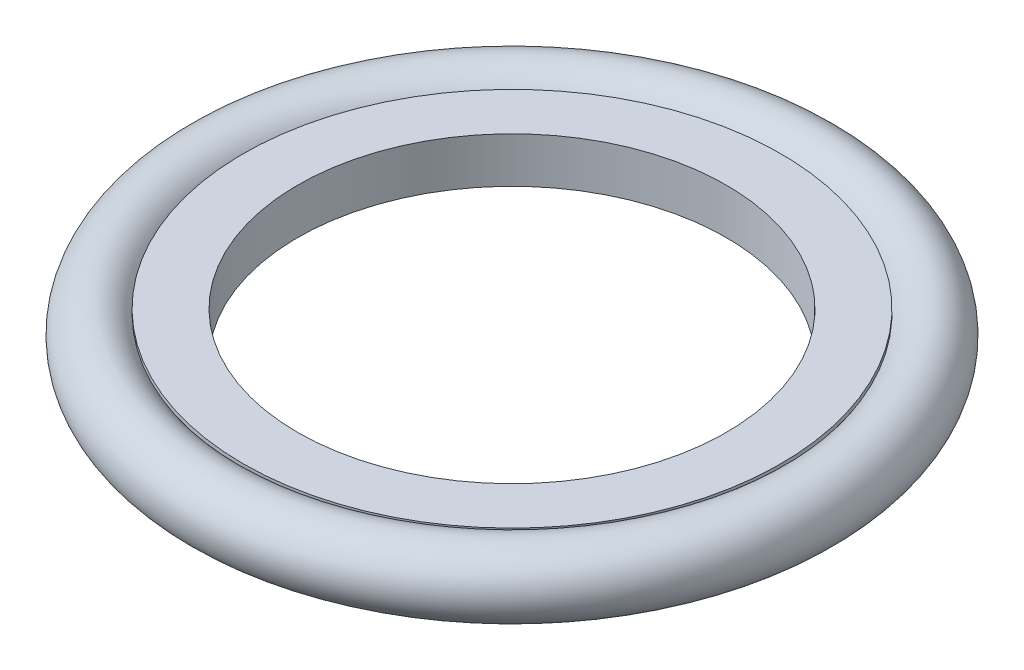
SolidWorks part; units mm, degrees
ref_plane "Front Plane" through (0, 0, 0) normal (0, 0, 1) x (1, 0, 0)
ref_plane "Top Plane" through (0, 0, 0) normal (0, 1, 0) x (1, 0, 0)
ref_plane "Right Plane" through (0, 0, 0) normal (1, 0, 0) x (0, 0, -1)
sketch "Sketch2" plane through (0, 0, 0) normal (1, 0, 0) x (0, 0, -1)
  line L0 (0, 0) -> (209.55, 0) construction
  line L1 (139.7, 0) -> (-139.7, 0) construction
  line L2 (209.55, 0) -> (254, 0) construction
  line L3 (209.55, 17.4625) -> (209.55, -17.4625) construction
  line L4 (0, 0) -> (0, -50000) construction
  circle A0 centre (228.3449, 0) radius 25.6551
  point P8 (209.55, 0)
  dimension "D4" = 51.3103
  dimension "D1" = 209.55
  dimension "D2" = 254
  dimension "D3" = 34.925
revolve "Revolve2" add sketch "Sketch2" angle 360 about L4
sketch "Sketch3" plane through (0, 0, 0) normal (1, 0, 0) x (0, 0, -1)
  line L0 (228.3449, 0) -> (50228.3449, 0) construction
  line L9 (209.6092, 17.526) -> (209.6092, -17.526) construction
  line L10 (207.0791, 17.526) -> (207.0791, 14.351)
  line L11 (207.0791, 14.351) -> (168.3342, 14.351)
  line L12 (168.3342, 14.351) -> (168.3342, -14.351)
  line L13 (207.0791, 17.526) -> (165.1592, 17.526)
  line L14 (165.1592, 17.526) -> (165.1592, -17.526)
  line L15 (207.0791, -17.526) -> (165.1592, -17.526)
  line L16 (207.0791, -14.351) -> (168.3342, -14.351)
  line L17 (207.0791, -17.526) -> (207.0791, -14.351)
  line L18 (0, 0) -> (0, -50000) construction
  circle A1 centre (228.3449, 0) radius 25.6551
  circle A2 centre (228.3449, 0) radius 25.6551 construction
  point P9 (0, 0)
  point P16 (165.1592, 0)
  point P18 (168.3342, 0)
  dimension "D2" = 35.052
  dimension "D3" = 3.175
  dimension "D4" = 3.175
  dimension "D5" = 44.45
  dimension "D1" = 0
revolve "Revolve3" add sketch "Sketch3" angle 360 about L18 other way angle 360
